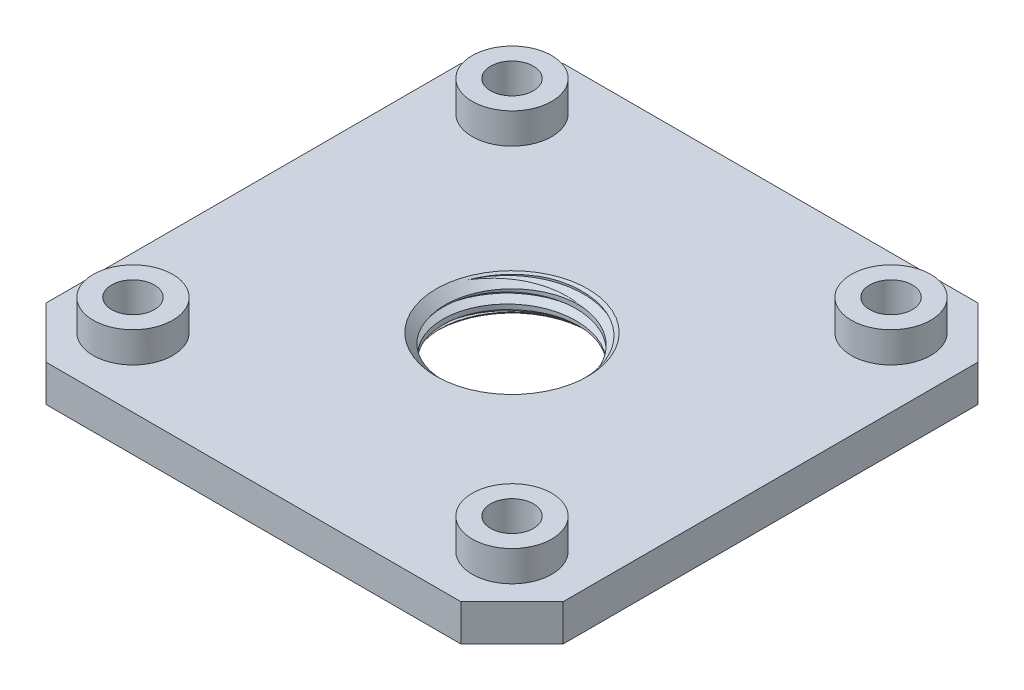
SolidWorks part; units mm, degrees
ref_plane "Front Plane" through (0, 0, 0) normal (0, 0, 1) x (1, 0, 0)
ref_plane "Top Plane" through (0, 0, 0) normal (0, 1, 0) x (1, 0, 0)
ref_plane "Right Plane" through (0, 0, 0) normal (1, 0, 0) x (0, 0, -1)
sketch "Sketch1" plane through (0, 0, 0) normal (0, 1, 0) x (1, 0, 0)
  line L1 (-21.15, 21.15) -> (21.15, 21.15)
  line L2 (-21.15, 21.15) -> (-21.15, -21.15)
  line L3 (-21.15, -21.15) -> (21.15, -21.15)
  line L4 (21.15, 21.15) -> (21.15, -21.15)
  line L5 (-21.15, 21.15) -> (21.15, -21.15) construction
  line L6 (-21.15, -21.15) -> (21.15, 21.15) construction
  point P0 (0, 0)
  dimension "D1" = 42.3
extrude "Boss-Extrude1" add sketch "Sketch1" along normal blind 3
ref_plane "Plane1" through (0, 0.8, 0) normal (0, -1, 0) x (-1, 0, 0)
ref_plane "Plane2" through (0, 7, 0) normal (0, -1, 0) x (-1, 0, 0)
sketch "Sketch2" plane through (0, 0.8, 0) normal (0, -1, 0) x (-1, 0, 0)
  line L0 (-21.15, 21.15) -> (21.15, 21.15) construction
  line L1 (11.0851, 0) -> (5.5426, 9.6)
  line L2 (5.5426, 9.6) -> (-5.5426, 9.6)
  line L3 (-5.5426, 9.6) -> (-11.0851, 0)
  line L4 (-11.0851, 0) -> (-5.5426, -9.6)
  line L5 (-5.5426, -9.6) -> (5.5426, -9.6)
  line L6 (5.5426, -9.6) -> (11.0851, 0)
  circle A0 centre (0, 0) radius 9.6 construction
  dimension "D1" = 19.2
extrude "Cut-Extrude1" [suppressed] cut sketch "Sketch2" against normal up to surface (6.2 mm away) contours L2 L3 L4 L5 L6 L1 up to plane "Plane2"
sketch "Sketch4" plane through (0, 0, 0) normal (0, 1, 0) x (1, 0, 0)
  line L0 (-21.15, 16.9631) -> (-16.9631, 21.15)
  line L1 (-21.15, 21.15) -> (-21.15, -21.15) construction
  line L2 (21.15, 21.15) -> (-21.15, 21.15) construction
  line L3 (16.9631, -21.15) -> (21.15, -16.9631)
  line L4 (-21.15, -21.15) -> (21.15, -21.15) construction
  line L5 (21.15, -21.15) -> (21.15, 21.15) construction
  line L6 (-21.15, 16.9631) -> (-21.15, 21.15)
  line L7 (-21.15, 21.15) -> (-16.9631, 21.15)
  line L8 (21.15, -16.9631) -> (21.15, -21.15)
  line L9 (21.15, -21.15) -> (16.9631, -21.15)
  dimension "D1" = 53.9
  dimension "D2" = 45
extrude "Cut-Extrude3" cut sketch "Sketch4" against normal through all and the other way through all
mirror "Mirror1" about plane through (0, 0, 0) normal (0, 0, 1) of "Cut-Extrude3"
sketch "Sketch6" plane through (0, 3, 0) normal (0, 1, 0) x (1, 0, 0)
  circle A0 centre (-15.5, 15.5) radius 3.25
  dimension "D1" = 6.5
  dimension "D2" = 15.5
  dimension "D3" = 15.5
extrude "Boss-Extrude2" add sketch "Sketch6" along normal blind 2.5
sketch "Sketch7" plane through (0, 0, 0) normal (0, 1, 0) x (1, 0, 0)
  circle A0 centre (-15.5, 15.5) radius 1.75
  dimension "D1" = 3.5
extrude "Cut-Extrude6" cut sketch "Sketch7" along normal through all
sketch "Sketch10" plane through (0, 0, 0) normal (0, 1, 0) x (-1, 0, 0)
  circle A0 centre (15.5, -15.5) radius 3
  circle A1 centre (15.5, -15.5) radius 1.75 construction
  dimension "D1" = 6
extrude "Cut-Extrude9" [suppressed] cut sketch "Sketch10" along normal blind 3.25
mirror "Mirror4" about plane through (0, 0, 0) normal (1, 0, 0) of "Cut-Extrude9", "Boss-Extrude2", "Cut-Extrude6"
mirror "Mirror5" about plane through (0, 0, 0) normal (0, 0, 1) of "Mirror4"
sketch "Sketch8" plane through (0, 0, 0) normal (0, 1, 0) x (1, 0, 0)
  circle A0 centre (0, 0) radius 7
  dimension "D1" = 14
extrude "Cut-Extrude7" [suppressed] cut sketch "Sketch8" along normal through all
sketch "Sketch11" plane through (0, 0, 0) normal (0, -1, 0) x (1, 0, 0)
  line L0 (-21.15, 0) -> (-14.8837, 0) construction
  line L1 (-21.15, -16.9631) -> (-21.15, 16.9631) construction
  line L2 (-21.15, 1) -> (-14.8837, 1)
  line L3 (-21.15, -1) -> (-14.8837, -1)
  arc A0 (-21.15, 1) -> (-21.15, -1) centre (-21.15, 0) ccw
  arc A1 (-14.8837, -1) -> (-14.8837, 1) centre (-14.8837, 0) ccw
  point P5 (-18.0169, 0)
  dimension "D1" = 2
extrude "Cut-Extrude10" [suppressed] cut sketch "Sketch11" against normal blind 2
split "Split1" [suppressed] bodies to split 113
chamfer "Chamfer1" [suppressed] distance 0.75 angle 45
sketch "Sketch12" plane through (0, 3, 0) normal (0, 1, 0) x (1, 0, 0)
  circle A0 centre (0, 0) radius 5.45
  dimension "D1" = 10.9
extrude "Cut-Extrude11" cut sketch "Sketch12" against normal through all
chamfer "Chamfer2" distance 0.75 angle 45 2 edges at (0, 0, 5.45) (0, 3, 5.45)
sketch "Sketch13" plane through (0, 3, 0) normal (0, 1, 0) x (1, 0, 0)
  circle A0 centre (0, 0) radius 5.45 construction
  circle A1 centre (0, 0) radius 5.45
curve "Helix/Spiral1" pitch 1.25 height 3.75 radius 5.45 centre (0, 3, 0) axis (0, -1, 0) start towards (0, 0, 1)
sketch "Sketch14" plane through (0, 0, 0) normal (0, 0, 1) x (1, 0, 0)
  line L0 (-5.45, 2.5736) -> (-5.45, 3.4264)
  line L1 (-5.45, 3.4264) -> (-6.05, 3.08)
  line L2 (-6.05, 3.08) -> (-6.05, 2.92)
  line L3 (-6.05, 2.92) -> (-5.45, 2.5736)
  line L4 (6.2, 3) -> (-6.2, 3) construction
  spline S1 degree 3 poles (-5.45, 3) (-5.45, 2.9741) (-5.1662, 2.9218) (-3.9541, 2.8438) (-2.1399, 2.7656) (0, 2.6875) (2.1399, 2.6094) (3.9541, 2.5313) (5.1662, 2.4531) (5.5919, 2.375) (5.1662, 2.2969) (3.9541, 2.2188) (1.5352, 2.1146) (-1.5352, 2.0104) (-3.9541, 1.9063) (-5.1662, 1.8281) (-5.5919, 1.75) (-5.1662, 1.6719) (-3.9541, 1.5938) (-1.5352, 1.4896) (1.5352, 1.3854) (3.9541, 1.2812) (5.1662, 1.2031) (5.5919, 1.125) (5.1662, 1.0469) (3.9541, 0.9687) (1.5352, 0.8646) (-1.5352, 0.7604) (-3.9541, 0.6562) (-5.1662, 0.5781) (-5.5919, 0.5) (-5.1662, 0.4219) (-3.9541, 0.3437) (-1.5352, 0.2396) (1.5352, 0.1354) (3.9541, 0.0312) (5.1662, -0.0469) (5.5919, -0.125) (5.1662, -0.2031) (3.9541, -0.2813) (2.1399, -0.3594) (0, -0.4375) (-2.1399, -0.5156) (-3.9541, -0.5938) (-5.1662, -0.6718) (-5.45, -0.7241) (-5.45, -0.75) knots 0 0 0 0 0.020833 0.041667 0.0625 0.083333 0.104167 0.125 0.145833 0.166667 0.1875 0.208333 0.229167 0.270833 0.291667 0.3125 0.333333 0.354167 0.375 0.395833 0.4375 0.458333 0.479167 0.5 0.520833 0.541667 0.5625 0.604167 0.625 0.645833 0.666667 0.6875 0.708333 0.729167 0.770833 0.791667 0.8125 0.833333 0.854167 0.875 0.895833 0.916667 0.9375 0.958333 0.979167 1 1 1 1 construction
  point P6 (-5.45, 3)
  dimension "D1" = 60
  dimension "D3" = 0.16
  dimension "D4" = 0.6
sweep "Cut-Sweep1" cut profiles "Sketch14" path "Helix/Spiral1" align with end faces yes
